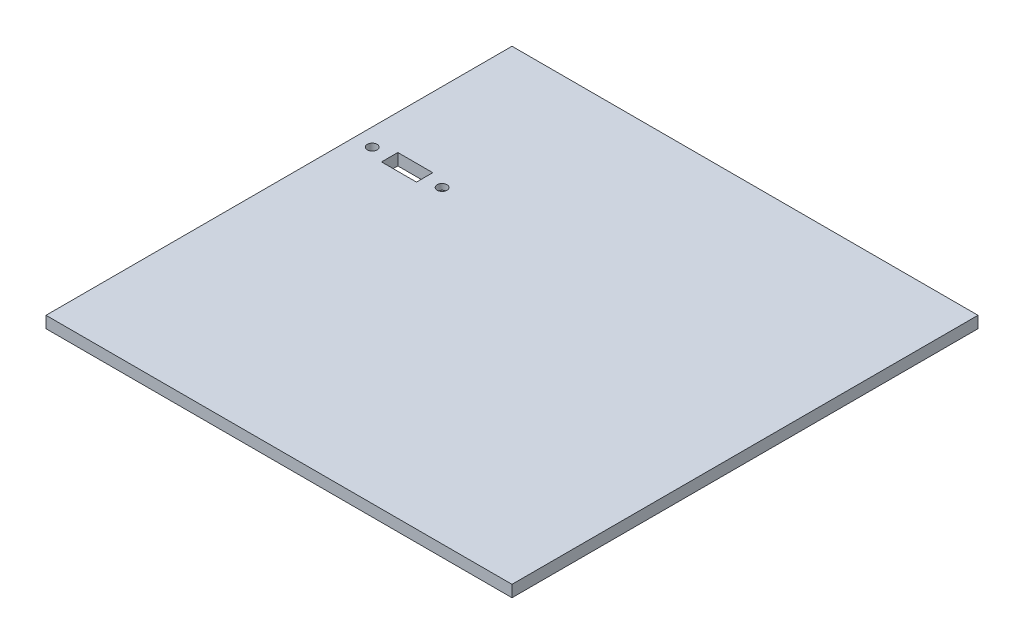
SolidWorks part; units mm, degrees
ref_plane "Front Plane" through (0, 0, 0) normal (0, 0, 1) x (1, 0, 0)
ref_plane "Top Plane" through (0, 0, 0) normal (0, 1, 0) x (1, 0, 0)
ref_plane "Right Plane" through (0, 0, 0) normal (1, 0, 0) x (0, 0, -1)
sketch "Sketch1" plane through (0, 0, 0) normal (0, 1, 0) x (1, 0, 0)
  line L1 (100, -100) -> (-100, -100)
  line L2 (100, -100) -> (100, 100)
  line L3 (100, 100) -> (-100, 100)
  line L4 (-100, -100) -> (-100, 100)
  line L5 (100, -100) -> (-100, 100) construction
  line L6 (100, 100) -> (-100, -100) construction
  point P0 (0, 0)
  dimension "D1" = 200
  dimension "D2" = 200
extrude "Boss-Extrude1" add sketch "Sketch1" along normal blind 5
sketch "Sketch3" plane through (0, 0, 0) normal (0, -1, 0) x (1, 0, 0)
  line L1 (59, -59) -> (-59, -59)
  line L2 (59, -59) -> (59, 59)
  line L3 (59, 59) -> (-59, 59)
  line L4 (-59, -59) -> (-59, 59)
  line L5 (59, -59) -> (-59, 59) construction
  line L6 (59, 59) -> (-59, -59) construction
  point P0 (0, 0)
  dimension "D1" = 118
  dimension "D2" = 118
extrude "Boss-Extrude2" add sketch "Sketch3" along normal blind 4 contours L1 L4 L3 L2
sketch "Sketch4" plane through (0, -4, 0) normal (0, -1, 0) x (1, 0, 0)
  line L1 (0, -65.89) -> (0, 65.89) construction
  line L2 (65.89, 0) -> (-65.89, 0) construction
  circle A0 centre (50, -50) radius 2.4
  circle A7 centre (-50, -50) radius 2.4
  circle A8 centre (-50, 50) radius 2.4
  circle A9 centre (50, 50) radius 2.4
  point P15 (0, 0)
  point P16 (0, 0)
  dimension "D1" = 4.8
  dimension "D2" = 50
  dimension "D4" = 4
  dimension "D3" = 50
extrude "Cut-Extrude1" cut sketch "Sketch4" against normal blind 8
sketch "Sketch7" plane through (0, -4, 0) normal (0, -1, 0) x (1, 0, 0)
  line L0 (50, 54.2724) -> (46.3, 52.1362)
  line L1 (-50, 54.2724) -> (-53.7, 52.1362)
  line L2 (-53.7, 52.1362) -> (-53.7, 47.8638)
  line L3 (-53.7, 47.8638) -> (-50, 45.7276)
  line L4 (-50, 45.7276) -> (-46.3, 47.8638)
  line L5 (-46.3, 47.8638) -> (-46.3, 52.1362)
  line L6 (-46.3, 52.1362) -> (-50, 54.2724)
  line L7 (46.3, 52.1362) -> (46.3, 47.8638)
  line L8 (46.3, 47.8638) -> (50, 45.7276)
  line L9 (50, 45.7276) -> (53.7, 47.8638)
  line L10 (53.7, 47.8638) -> (53.7, 52.1362)
  line L11 (53.7, 52.1362) -> (50, 54.2724)
  line L12 (50, -45.7276) -> (46.3, -47.8638)
  line L13 (46.3, -47.8638) -> (46.3, -52.1362)
  line L14 (46.3, -52.1362) -> (50, -54.2724)
  line L15 (50, -54.2724) -> (53.7, -52.1362)
  line L16 (53.7, -52.1362) -> (53.7, -47.8638)
  line L17 (53.7, -47.8638) -> (50, -45.7276)
  line L18 (-50, -45.7276) -> (-53.7, -47.8638)
  line L19 (-53.7, -47.8638) -> (-53.7, -52.1362)
  line L20 (-53.7, -52.1362) -> (-50, -54.2724)
  line L21 (-50, -54.2724) -> (-46.3, -52.1362)
  line L22 (-46.3, -52.1362) -> (-46.3, -47.8638)
  line L23 (-46.3, -47.8638) -> (-50, -45.7276)
  circle A0 centre (-50, 50) radius 3.7 construction
  circle A2 centre (50, 50) radius 3.7 construction
  circle A3 centre (50, -50) radius 3.7 construction
  circle A4 centre (-50, -50) radius 3.7 construction
  dimension "D1" = 7.4
  dimension "D2" = 2
  dimension "D3" = 2
extrude "Cut-Extrude3" cut sketch "Sketch7" against normal blind 3.6 from offset 2 offset against normal yes
sketch "Sketch6" plane through (0, -4, 0) normal (0, -1, 0) x (1, 0, 0)
  line L0 (100, -100) -> (-100, -100) construction
  line L1 (-40, -36) -> (-85, -36)
  line L2 (-40, -36) -> (-40, -29)
  line L3 (-40, -29) -> (-85, -29)
  line L4 (-85, -36) -> (-85, -29)
  line L7 (-100, -100) -> (-100, 100) construction
  dimension "D1" = 64
  dimension "D2" = 7
  dimension "D3" = 45
  dimension "D4" = 15
extrude "Cut-Extrude2" cut sketch "Sketch6" against normal blind 6.5
sketch "Sketch8" plane through (0, 5, 0) normal (0, 1, 0) x (1, 0, 0)
  line L0 (-100, 100) -> (-100, -100) construction
  line L1 (-85, 36) -> (-70, 36)
  line L2 (-85, 36) -> (-85, 29)
  line L3 (-85, 29) -> (-70, 29)
  line L4 (-70, 36) -> (-70, 29)
  line L5 (100, 100) -> (-100, 100) construction
  dimension "D1" = 15
  dimension "D2" = 15
  dimension "D3" = 7
  dimension "D4" = 64
extrude "Cut-Extrude4" cut sketch "Sketch8" against normal through all
sketch "Sketch9" plane through (0, 0, 0) normal (0, -1, 0) x (1, 0, 0)
  line L0 (-85, -32.5) -> (-70, -32.5) construction
  line L1 (-85, -36) -> (-85, -29) construction
  line L2 (-70, -36) -> (-70, -29) construction
  line L3 (-77.5, -32.5) -> (-77.5, -29) construction
  line L4 (-85, -29) -> (-59, -29) construction
  circle A0 centre (-62.5, -32.5) radius 2.1
  circle A1 centre (-92.5, -32.5) radius 2.1
  dimension "D1" = 4.2
  dimension "D2" = 30
extrude "Cut-Extrude5" cut sketch "Sketch9" against normal through all
